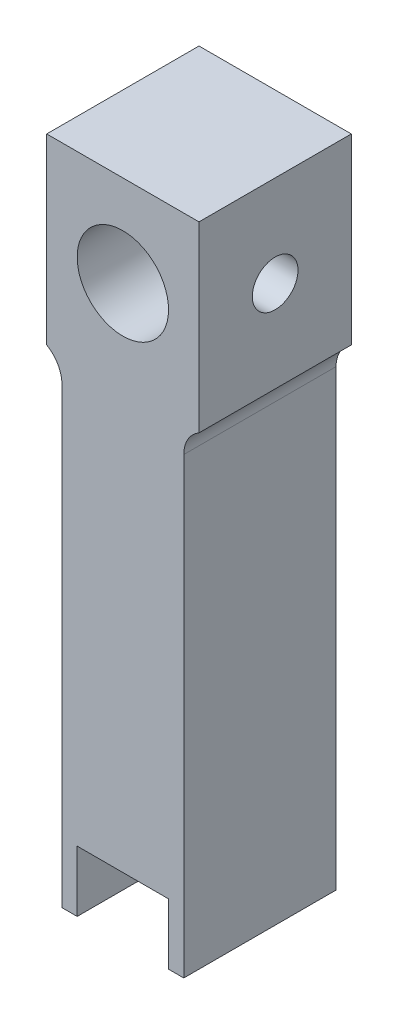
SolidWorks part; units mm, degrees
ref_plane "Front Plane" through (0, 0, 0) normal (0, 0, 1) x (1, 0, 0)
ref_plane "Top Plane" through (0, 0, 0) normal (0, 1, 0) x (1, 0, 0)
ref_plane "Right Plane" through (0, 0, 0) normal (1, 0, 0) x (0, 0, -1)
sketch "Sketch1" plane through (0, 0, 0) normal (0, 0, 1) x (1, 0, 0)
  line L1 (-5, 6) -> (5, 6)
  line L2 (-5, 6) -> (-5, -6)
  line L3 (-5, -6) -> (5, -6)
  line L4 (5, 6) -> (5, -6)
  line L5 (-5, 6) -> (5, -6) construction
  line L6 (-5, -6) -> (5, 6) construction
  line L7 (-5, -6) -> (-1, -6)
  line L15 (-4, -6) -> (4, -6)
  line L16 (-4, -6) -> (-4, -37.5)
  line L17 (-4, -37.5) -> (-3, -37.5)
  line L22 (4, -6) -> (4, -37.5)
  line L23 (-3, -37.5) -> (-3, -33.5)
  line L24 (3, -37.5) -> (3, -33.5)
  line L25 (-3, -33.5) -> (3, -33.5)
  line L26 (3, -37.5) -> (4, -37.5)
  circle A0 centre (0, 0) radius 3
  point P1 (0, 0)
  point P11 (0, -6)
  point P12 (0, -6)
  dimension "D8" = 6
  dimension "D1" = 10
  dimension "D2" = 12
  dimension "D3" = 8
  dimension "D4" = 31.5
  dimension "D5" = 6
  dimension "D6" = 4
extrude "Boss-Extrude1" add sketch "Sketch1" along normal blind 10 contours L4 L1 L2 L3 A0 | L3 | L3 region at (0, 5.8438, 0) region at (0, -20.3026, 0)
sketch "Sketch2" plane through (-5, 0, 0) normal (-1, 0, 0) x (0, 0, 1)
  line L0 (10, 6) -> (0, 6) construction
  circle A0 centre (5, 0) radius 1.5
  point P2 (0, 0)
  point P5 (5, 6)
  dimension "D1" = 3
extrude "Cut-Extrude1" cut sketch "Sketch2" against normal through all
fillet "Fillet1" radius 2 2 edges at (4, -6, 5) (-4, -6, 5)
